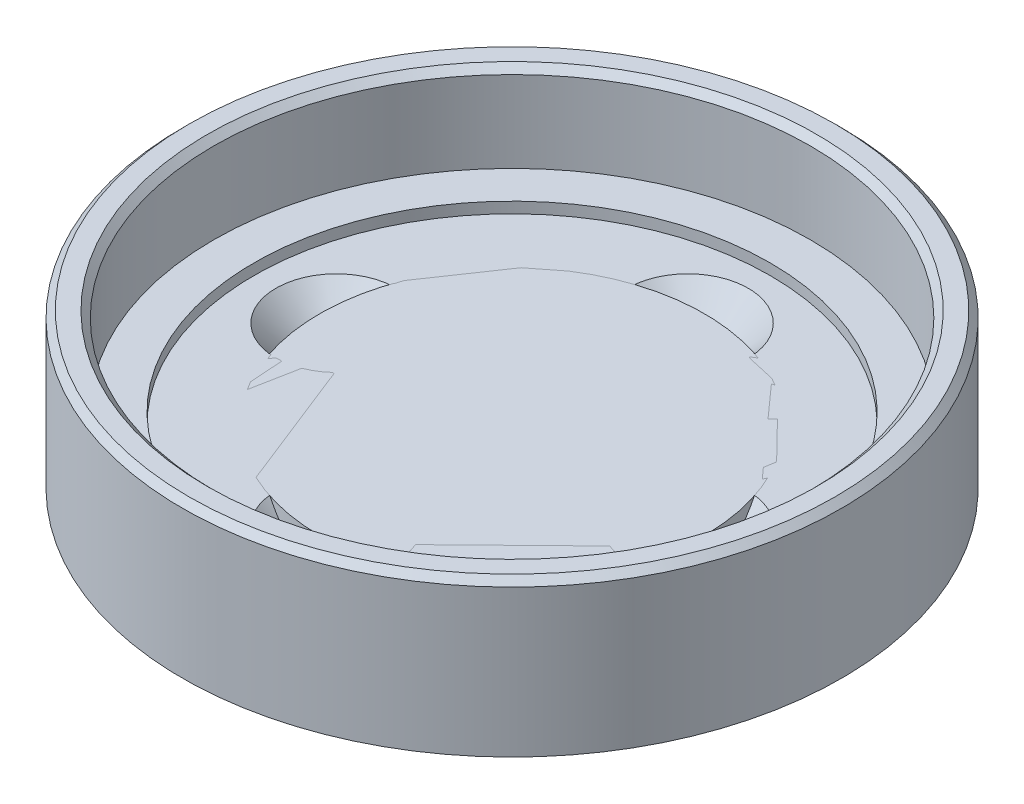
SolidWorks part; units mm, degrees
ref_plane "Front Plane" through (0, 0, 0) normal (0, 0, 1) x (1, 0, 0)
ref_plane "Top Plane" through (0, 0, 0) normal (0, 1, 0) x (1, 0, 0)
ref_plane "Right Plane" through (0, 0, 0) normal (1, 0, 0) x (0, 0, -1)
sketch "Sketch1" plane through (0, 0, 0) normal (0, 1, 0) x (1, 0, 0)
  circle A0 centre (0, 0) radius 15
  dimension "D1" = 30
extrude "Boss-Extrude1" add sketch "Sketch1" along normal blind 6.2
sketch "Sketch2" plane through (0, 6.2, 0) normal (0, 1, 0) x (1, 0, 0)
  circle A0 centre (0, 0) radius 11.75
  dimension "D1" = 23.5
extrude "Cut-Extrude1" cut sketch "Sketch2" against normal blind 0.5
sketch "Sketch3" plane through (0, 6.2, 0) normal (0, 1, 0) x (1, 0, 0)
  circle A0 centre (0, 0) radius 13.575
  circle A1 centre (0, 0) radius 15
  circle A2 centre (0, 0) radius 15 construction
  dimension "D1" = 27.15
extrude "Boss-Extrude2" add sketch "Sketch3" along normal blind 4
sketch "Sketch4" plane through (0, 5.7, 0) normal (0, 1, 0) x (1, 0, 0)
  circle A0 centre (0, 0) radius 1.65
  dimension "D1" = 3.3
extrude "Cut-Extrude2" cut sketch "Sketch4" against normal through all
ref_plane "Plane1" through (3.75, 0, 0) normal (1, 0, 0) x (0, 0, -1)
sketch "Sketch5" plane through (0, 0, 0) normal (1, 0, 0) x (0, 0, -1)
  line L1 (1.65, 5.7) -> (-1.65, 5.7) construction
  line L2 (-2.875, -0.05) -> (2.875, -0.05) construction
  line L3 (-2.875, -0.05) -> (-2.875, 5.7) construction
  line L4 (-2.875, 5.7) -> (2.875, 5.7) construction
  line L5 (2.875, -0.05) -> (2.875, 5.7) construction
  line L6 (-2.875, -0.05) -> (2.875, 5.7) construction
  line L7 (-2.875, 5.7) -> (2.875, -0.05) construction
  circle A0 centre (0, 2.825) radius 1.65
  dimension "D1" = 3.3
  dimension "D2" = 5.75
extrude "Cut-Extrude3" [suppressed] cut sketch "Sketch5" along normal through all
sketch "Sketch6" plane through (0, 0, 0) normal (0, -1, 0) x (1, 0, 0)
  circle A0 centre (0, 0) radius 1.65 construction
  circle A1 centre (0, 0) radius 1.65
  circle A2 centre (0, 0) radius 16.5
  dimension "D1" = 33
extrude "Boss-Extrude3" add sketch "Sketch6" along normal blind 1
sketch "Sketch7" [suppressed] plane through (3.75, 0, 0) normal (1, 0, 0) x (0, 0, -1)
  line L7 (-2.875, 5.7) -> (2.875, 5.7)
  line L8 (-2.875, 5.7) -> (-2.875, -0.05)
  line L9 (-2.875, -0.05) -> (2.875, -0.05)
  line L10 (2.875, 5.7) -> (2.875, -0.05)
  line L11 (-2.875, 5.7) -> (2.875, -0.05) construction
  line L12 (-2.875, -0.05) -> (2.875, 5.7) construction
  point P1 (0, 2.825)
  dimension "D2" = 5.75
extrude "Cut-Extrude4" [suppressed] cut sketch "Sketch7" along normal blind 1.85
ref_axis "Axis1" [suppressed] through (0, 10.2, 0) along (0, -1, 0)
pattern_circular "CirPattern1" [suppressed] count 2 over 360 about axis through (0, 10.2, 0) along (0, -1, 0) of bodies 107
ref_plane "Plane2" [suppressed] through (0, 0, 0) normal (0, 0, 1) x (0, -1, 0)
ref_plane "Plane3" [suppressed] through (0, 0, 12.6) normal (0, 0, 1) x (0, -1, 0)
sketch "Sketch11" [suppressed] plane through (0, 0, 12.6) normal (0, 0, 1) x (0, -1, 0)
  line L0 (0, 23.2225) -> (0, -23.2225) construction
  point P4 (0, 0)
ref_plane "Plane4" [suppressed] through (0, 2.5624, 12.0553) normal (0, 0.2079, 0.9781) x (-1, 0, 0)
sketch "Sketch9" [suppressed] plane through (0, 0.4393, 12.5066) normal (0, 0.2079, 0.9781) x (0, -0.9781, 0.2079)
  line L0 (-12.1477, 0) -> (-2.1706, 0) construction
  line L2 (1.4491, 2.9) -> (-4.3509, 2.9) construction
  line L3 (1.4491, 2.9) -> (1.4491, -2.9) construction
  line L4 (1.4491, -2.9) -> (-4.3509, -2.9) construction
  line L5 (-4.3509, 2.9) -> (-4.3509, -2.9) construction
  line L6 (1.4491, 2.9) -> (-4.3509, -2.9) construction
  line L7 (1.4491, -2.9) -> (-4.3509, 2.9) construction
  line L8 (0.4491, 23.2225) -> (0.4491, -23.2225) construction
  circle A0 centre (-1.4509, 0) radius 1.65
  dimension "D2" = 3.3
  dimension "D1" = 5.8
  dimension "D3" = 1
extrude "Cut-Extrude5" [suppressed] cut sketch "Sketch9" along normal through all and the other way blind 2
sketch "Sketch10" [suppressed] plane through (0, 0.0203, 12.5957) normal (0, 0.2079, 0.9781) x (0, -0.9781, 0.2079)
  line L1 (1.0208, 2.9) -> (-4.7792, 2.9) construction
  line L2 (-4.7792, 2.9) -> (-4.7792, -2.9) construction
  line L3 (1.0208, -2.9) -> (-4.7792, -2.9) construction
  line L5 (1.0208, 2.9) -> (-4.7792, 2.9)
  line L6 (-4.7792, 2.9) -> (-4.7792, -2.9)
  line L7 (1.0208, -2.9) -> (-4.7792, -2.9)
  line L8 (1.0208, 2.9) -> (3.0208, 2.9)
  line L9 (3.0208, 2.9) -> (3.0208, -2.9)
  line L10 (3.0208, -2.9) -> (1.0208, -2.9)
  dimension "D1" = 2
extrude "Cut-Extrude6" [suppressed] cut sketch "Sketch10" along normal blind 1.8
ref_plane "Plane5" [suppressed] through (0, 2.2506, 10.5881) normal (0, 0.2079, 0.9781) x (-1, 0, 0)
sketch "Sketch13" [suppressed] plane through (0, 2.2506, 10.5881) normal (0, 0.2079, 0.9781) x (-1, 0, 0)
  line L0 (-2.0203, -0.0157) -> (-3.3435, 3.6197)
  line L1 (-3.3435, 3.6197) -> (3.3435, 3.6197)
  line L2 (3.3435, 3.6197) -> (2.0203, -0.0157)
  line L3 (0, 0.7197) -> (0, 3.6197) construction
  line L4 (-2.9, 3.6197) -> (2.9, 3.6197) construction
  circle A0 centre (0, 0.7197) radius 1.65 construction
  circle A1 centre (0, 0.7197) radius 1.65 construction
  circle A2 centre (0, 0.7197) radius 2.15 construction
  arc A3 (2.0203, -0.0157) -> (-2.0203, -0.0157) centre (0, 0.7197) cw
  dimension "D1" = 20
  dimension "D2" = 0.5
ref_plane "Plane6" [suppressed] through (0, 0, 0) normal (-1, 0, 0) x (0, -1, 0)
ref_plane "Plane7" [suppressed] through (0, 0, 15.05) normal (0, 0, 1) x (1, 0, 0)
sketch "Sketch14" [suppressed] plane through (0, 0, 0) normal (-1, 0, 0) x (0, -1, 0)
  line L0 (-3.1606, 10.3947) -> (3.3348, 0) construction
  line L3 (0.0673, 11.0808) -> (-3.1606, 10.3947) construction
  line L5 (-3.1606, 10.3947) -> (-0.9781, 0.1272) construction
  arc A0 (-3.1606, 10.3947) -> (3.3348, 0) centre (14.3667, 14.1202) ccw
  dimension "D1" = 70
sweep "Cut-Sweep1" [suppressed] cut profiles "Sketch13" path "Sketch14"
sketch "Sketch19" [suppressed] plane through (0, 0, 15.05) normal (0, 0, 1) x (1, 0, 0)
  line L0 (2.9, 5.0693) -> (-2.9, 5.0693) construction
  line L1 (2.9, 5.0693) -> (-2.9, 5.0693) construction
  line L2 (15.05, 0) -> (-15.05, 0) construction
  line L3 (2.9, 0) -> (-2.9, 0) construction
  line L4 (-2.9, 5.0693) -> (-2.9, 0) construction
  line L5 (2.9, 5.0693) -> (2.9, 0) construction
  line L6 (-2.9, 4.1501) -> (2.9, 4.1501)
  line L7 (2.9, 4.1501) -> (2.9, 0)
  line L8 (2.9, 0) -> (-2.9, 0)
  line L9 (-2.9, 0) -> (-2.9, 4.1501)
  spline S0 degree 3 poles (-0.1103, 0.7763) (0.2206, 0.7763) (0.4399, 0.8212) (0.8405, 0.99) (1.0254, 1.1159) (1.2534, 1.3496) (1.3227, 1.4364) (1.4409, 1.6193) (1.4906, 1.7158) (1.5713, 1.9192) (1.6017, 2.0256) (1.6413, 2.2394) (1.6508, 2.3479) (1.6481, 2.6783) (1.6048, 2.894) (1.4812, 3.1989) (1.4311, 3.2954) (1.313, 3.4783) (1.2443, 3.5654) (1.0179, 3.8015) (0.8351, 3.9301) (0.4362, 4.1039) (0.2169, 4.1502) (-0.1103, 4.15) (-0.221, 4.1383) (-0.434, 4.0932) (-0.5375, 4.06) (-0.8386, 3.9282) (-1.0184, 3.8015) (-1.2465, 3.5629) (-1.3137, 3.4774) (-1.4314, 3.2948) (-1.4822, 3.1968) (-1.5642, 2.9938) (-1.5952, 2.8896) (-1.6378, 2.6758) (-1.6492, 2.5653) (-1.6515, 2.2381) (-1.6107, 2.0182) (-1.4501, 1.6141) (-1.3285, 1.4262) (-1.1006, 1.193) (-1.0155, 1.1218) (-0.835, 0.9992) (-0.7396, 0.9474) (-0.5381, 0.8627) (-0.4321, 0.8302) (-0.2188, 0.7873) (-0.1103, 0.7763) (0.2206, 0.7763) (0.4399, 0.8212) knots -0.03125 -0.03125 0 0 0.0625 0.0625 0.125 0.125 0.15625 0.15625 0.1875 0.1875 0.21875 0.21875 0.25 0.25 0.3125 0.3125 0.34375 0.34375 0.375 0.375 0.4375 0.4375 0.5 0.5 0.53125 0.53125 0.5625 0.5625 0.625 0.625 0.65625 0.65625 0.6875 0.6875 0.71875 0.71875 0.75 0.75 0.8125 0.8125 0.875 0.875 0.90625 0.90625 0.9375 0.9375 0.96875 0.96875 1 1 1.0625 1.0625 1.125 only from (0, 0.7763) to (0, 0.7763) construction
  spline S1 degree 3 poles (-0.1103, 0.7763) (0.2206, 0.7763) (0.4399, 0.8212) (0.8405, 0.99) (1.0254, 1.1159) (1.2534, 1.3496) (1.3227, 1.4364) (1.4409, 1.6193) (1.4906, 1.7158) (1.5713, 1.9192) (1.6017, 2.0256) (1.6413, 2.2394) (1.6508, 2.3479) (1.6481, 2.6783) (1.6048, 2.894) (1.4812, 3.1989) (1.4311, 3.2954) (1.313, 3.4783) (1.2443, 3.5654) (1.0179, 3.8015) (0.8351, 3.9301) (0.4362, 4.1039) (0.2169, 4.1502) (-0.1103, 4.15) (-0.221, 4.1383) (-0.434, 4.0932) (-0.5375, 4.06) (-0.8386, 3.9282) (-1.0184, 3.8015) (-1.2465, 3.5629) (-1.3137, 3.4774) (-1.4314, 3.2948) (-1.4822, 3.1968) (-1.5642, 2.9938) (-1.5952, 2.8896) (-1.6378, 2.6758) (-1.6492, 2.5653) (-1.6515, 2.2381) (-1.6107, 2.0182) (-1.4501, 1.6141) (-1.3285, 1.4262) (-1.1006, 1.193) (-1.0155, 1.1218) (-0.835, 0.9992) (-0.7396, 0.9474) (-0.5381, 0.8627) (-0.4321, 0.8302) (-0.2188, 0.7873) (-0.1103, 0.7763) (0.2206, 0.7763) (0.4399, 0.8212) knots -0.03125 -0.03125 0 0 0.0625 0.0625 0.125 0.125 0.15625 0.15625 0.1875 0.1875 0.21875 0.21875 0.25 0.25 0.3125 0.3125 0.34375 0.34375 0.375 0.375 0.4375 0.4375 0.5 0.5 0.53125 0.53125 0.5625 0.5625 0.625 0.625 0.65625 0.65625 0.6875 0.6875 0.71875 0.71875 0.75 0.75 0.8125 0.8125 0.875 0.875 0.90625 0.90625 0.9375 0.9375 0.96875 0.96875 1 1 1.0625 1.0625 1.125 only from (0, 0.7763) to (0, 0.7763) construction
extrude "Cut-Extrude11" [suppressed] cut sketch "Sketch19" against normal up to surface (0.6098 mm away)
pattern_circular "CirPattern2" [suppressed] count 2 over 360 about axis through (0, 10.2, 0) along (0, -1, 0) of bodies 119
sketch "Sketch16" [suppressed] plane through (0, -1, 0) normal (0, -1, 0) x (1, 0, 0)
  line L0 (0, 0) -> (-11.6673, 11.6673) construction
  line L1 (0, 11.1539) -> (0, -11.1539) construction
  circle A0 centre (0, 0) radius 16.5 construction
  circle A1 centre (-8.5913, 8.5913) radius 1.4
  circle A2 centre (-8.5913, 8.5913) radius 2.9 construction
  circle A3 centre (0, 0) radius 15.05 construction
  dimension "D2" = 2.8
  dimension "D3" = 5.8
  dimension "D1" = 45
extrude "Cut-Extrude8" [suppressed] cut sketch "Sketch16" against normal blind 4.5
sketch "Sketch17" [suppressed] plane through (0, 3.5, 0) normal (0, -1, 0) x (1, 0, 0)
  line L1 (-10.5918, 10.5918) -> (-11.324, 7.8591) construction
  line L2 (-11.324, 7.8591) -> (-9.3236, 5.8587)
  line L3 (-9.3236, 5.8587) -> (-6.5909, 6.5909)
  line L4 (-6.5909, 6.5909) -> (-5.8587, 9.3236)
  line L5 (-5.8587, 9.3236) -> (-7.8591, 11.324)
  line L6 (-7.8591, 11.324) -> (-10.5918, 10.5918) construction
  line L7 (-7.8591, 11.324) -> (-8.9095, 12.3744)
  line L8 (-8.9095, 12.3744) -> (-12.3744, 8.9095)
  line L9 (-12.3744, 8.9095) -> (-11.324, 7.8591)
  line L10 (-6.5909, 6.5909) -> (-8.5913, 8.5913) construction
  circle A0 centre (-8.5913, 8.5913) radius 2.45 construction
  circle A1 centre (0, 0) radius 15.05 construction
  dimension "D1" = 4.9
extrude "Cut-Extrude9" [suppressed] cut sketch "Sketch17" along normal blind 2.4
pattern_circular "CirPattern3" [suppressed] count 4 over 360 about axis through (0, 10.2, 0) along (0, -1, 0) of bodies 115
sketch "Sketch18" plane through (0, 5.7, 0) normal (0, 1, 0) x (1, 0, 0)
  circle A2 centre (0, 0) radius 2.9
  dimension "D1" = 5.8
extrude "Cut-Extrude10" cut sketch "Sketch18" against normal blind 0.7
sketch "Sketch20" [suppressed] plane through (0, 5.7, 0) normal (0, 1, 0) x (1, 0, 0)
  line L0 (3.75, 2.875) -> (3.75, -2.875) construction
  line L1 (-3.75, -2.875) -> (-3.75, 2.875) construction
  line L2 (3.75, 1.3919) -> (3.75, -1.3919)
  line L3 (-3.75, -1.3919) -> (-3.75, 1.3919)
  circle A0 centre (0, 0) radius 2.9 construction
  circle A1 centre (0, 0) radius 2.9
  arc A2 (3.75, 1.3919) -> (-3.75, 1.3919) centre (0, 0) ccw
  arc A3 (-3.75, -1.3919) -> (3.75, -1.3919) centre (0, 0) ccw
  dimension "D1" = 8
extrude "Boss-Extrude4" [suppressed] add sketch "Sketch20" along normal blind 2.5
fillet "Fillet2" [suppressed] radius 0.75
fillet "Fillet3" [suppressed] radius 0.2
sketch "Sketch21" [suppressed] plane through (0, 0, 0) normal (0, 0, 1) x (1, 0, 0)
  line L0 (13.575, 6.2) -> (-13.575, 6.2) construction
  line L1 (13.575, 6.2) -> (-13.575, 6.2) construction
  line L2 (0, 0) -> (0, 10.2954) construction
  line L3 (0, 10.2) -> (0, 0) construction
  line L4 (-14.9, 10.2) -> (-15.05, 5) construction
  line L5 (15.05, 10.2) -> (-15.05, 10.2) construction
  line L6 (-15.05, 10.2) -> (-15.05, 4.475) construction
  line L7 (-15.05, 5) -> (-15.05, 10.2)
  line L8 (-15.05, 10.2) -> (-14.9, 10.2)
  line L10 (-14.9447, 5.1824) -> (-14.8, 10.2)
  line L11 (-14.8, 10.2) -> (-14.9, 10.2)
  line L14 (-15.05, 5) -> (-14.9447, 5.1824)
  dimension "D1" = 0.15
  dimension "D2" = 30
  dimension "D3" = 1.2
  dimension "D4" = 0.1
sketch "Sketch22" [suppressed] plane through (0, 4.1501, 0) normal (0, -1, 0) x (1, 0, 0)
  line L0 (-2.9, 14.768) -> (2.9, 14.768)
  line L1 (2.9, 14.768) -> (2.9, 15.768)
  line L2 (2.9, 15.768) -> (-2.9, 15.768)
  line L3 (-2.9, 15.768) -> (-2.9, 14.768)
  line L4 (0, 0) -> (16.5, 0) construction
  line L5 (-2.9, -15.768) -> (-2.9, -14.768)
  line L6 (2.9, -15.768) -> (-2.9, -15.768)
  line L7 (2.9, -14.768) -> (2.9, -15.768)
  line L8 (-2.9, -14.768) -> (2.9, -14.768)
  circle A0 centre (0, 0) radius 16.5 construction
  dimension "D1" = 1
extrude "Cut-Extrude12" [suppressed] cut sketch "Sketch22" against normal blind 10
chamfer "Chamfer2" distance 0.3 angle 45 2 edges at (0, 10.2, 13.575) (0, 10.2, 15)
sketch "Sketch23" plane through (0, 5.7, 0) normal (0, 1, 0) x (1, 0, 0)
  circle A0 centre (0, 0) radius 8.75
  dimension "D1" = 17.5
extrude "Boss-Extrude5" add sketch "Sketch23" against normal blind 5 separate body
sketch "Sketch24" [suppressed] plane through (0, -1, 0) normal (0, -1, 0) x (1, 0, 0)
  line L0 (0, 0) -> (16.5, 0) construction
  line L1 (-2.9, 13.7327) -> (2.9, 13.7327)
  line L2 (-2.9, 13.7327) -> (-2.9, 18.7327)
  line L3 (-2.9, 18.7327) -> (2.9, 18.7327)
  line L4 (2.9, 13.7327) -> (2.9, 18.7327)
  line L5 (2.9, -13.7327) -> (2.9, -18.7327)
  line L6 (-2.9, -18.7327) -> (2.9, -18.7327)
  line L7 (-2.9, -13.7327) -> (-2.9, -18.7327)
  line L8 (-2.9, -13.7327) -> (2.9, -13.7327)
  line L9 (-2.9, 12.8126) -> (-2.9, 14.6528) construction
  line L10 (2.9, 14.6528) -> (2.9, 12.8126) construction
  circle A1 centre (0, 0) radius 16.5 construction
  dimension "D1" = 5
extrude "Cut-Extrude13" [suppressed] cut sketch "Sketch24" against normal up to surface (1 mm away)
fillet "Fillet4" [suppressed] radius 1
ref_plane "Plane8" through (0, 3.2, 0) normal (0, 1, 0) x (1, 0, 0)
sketch "Sketch27" plane through (0, 3.2, 0) normal (0, 1, 0) x (1, 0, 0)
  circle A0 centre (0, 0) radius 16.5
  circle A1 centre (0, 0) radius 16.5 construction
extrude "Cut-Extrude16" cut sketch "Sketch27" against normal blind 10
sketch "Sketch28" plane through (0, 5.7, 0) normal (0, 1, 0) x (1, 0, 0)
  circle A0 centre (0, 0) radius 8 construction
  circle A1 centre (0, 8) radius 1.25
  circle A2 centre (8, 0) radius 1.25
  circle A3 centre (0, -8) radius 1.25
  circle A4 centre (-8, 0) radius 1.25
  point P14 (0, 0)
  dimension "D1" = 16
  dimension "D2" = 2.5
  dimension "D3" = 4
extrude "Cut-Extrude17" cut sketch "Sketch28" against normal blind 10
hole_wizard "CSK for M2.5 Flat Head Machine Screw1" positions "Sketch29" profile "Sketch30" countersink size "M2.5" standard "ANSI Metric"
sketch "Sketch29" plane through (0, 5.7, 0) normal (0, 1, 0) x (1, 0, 0)
  point P0 (0, 8)
  point P3 (-8, 0)
  point P6 (8, 0)
  point P9 (0, -8)
sketch "Sketch30" plane through (0, 5.7, -8) normal (1, 0, 0) x (0, 0, 1)
  line L0 (0, 0) -> (0, 5.8412)
  line L1 (0, 5.8412) -> (1.4, 5)
  line L2 (1.4, 5) -> (1.4, 1.35)
  line L3 (1.4, 1.35) -> (2.75, 0)
  line L5 (2.75, 0) -> (0, 0)
  line L6 (-1.4, 1.35) -> (-2.75, 0) construction
  line L10 (0, 5.8412) -> (-1.4, 5) construction
  line L11 (0, -6.35) -> (0, 107.95) construction
  dimension "Hole Dia." = 2.8
  dimension "Hole Depth" = 5
  dimension "Near C'Sink Dia." = 5.5
  dimension "Near C'Sink Angle" = 90
  dimension "Drill Angle" = 118
